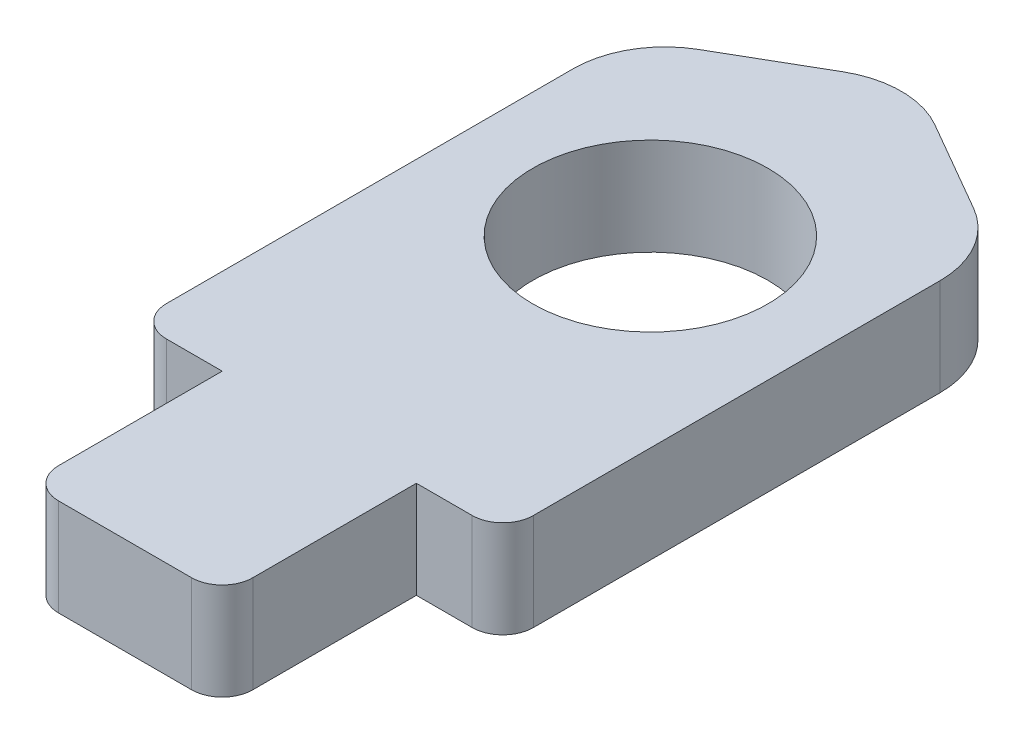
SolidWorks part; units mm, degrees
material "Beech"
ref_plane "Front Plane" through (0, 0, 0) normal (0, 0, 1) x (1, 0, 0)
ref_plane "Top Plane" through (0, 0, 0) normal (0, 1, 0) x (1, 0, 0)
ref_plane "Right Plane" through (0, 0, 0) normal (1, 0, 0) x (0, 0, -1)
sketch "Sketch2" plane through (0, 0, 0) normal (0, 1, 0) x (1, 0, 0)
  line L0 (-6, 5.205) -> (-5.4495, 5.205)
  line L1 (-6, 3.4729) -> (-6, -10.8257)
  line L2 (6, 3.4729) -> (6, -10.8257)
  line L3 (-6, -10.8257) -> (-3.175, -10.8257)
  line L4 (-4.5, 6.071) -> (-1.5, 7.8031)
  line L5 (-3.175, -10.8257) -> (-3.175, -17.1757)
  line L6 (-3.175, -17.1757) -> (3.175, -17.1757)
  line L7 (3.175, -17.1757) -> (3.175, -10.8257)
  line L8 (1.5, 7.8031) -> (4.5, 6.071)
  line L9 (3.175, -10.8257) -> (6, -10.8257)
  line L12 (5.4495, 5.205) -> (6, 5.205)
  circle A0 centre (0, 0) radius 3.845
  arc A1 (-4.5, 6.071) -> (-6, 3.4729) centre (-3, 3.4729) ccw
  arc A2 (4.5, 6.071) -> (6, 3.4729) centre (3, 3.4729) cw
  arc A3 (1.5, 7.8031) -> (-1.5, 7.8031) centre (0, 5.205) ccw
  point P3 (0, 5.205)
  point P14 (0, -17.1757)
  dimension "D1" = 7.69
  dimension "D9" = 3
  dimension "D10" = 3
  dimension "D11" = 3
  dimension "D2" = 5.205
  dimension "D3" = 16.0307
  dimension "D4" = 12
  dimension "D5" = 6.35
  dimension "D6" = 6.35
  dimension "D8" = 30
extrude "MotorMount_Extrude" add sketch "Sketch2" along normal blind 3.175 contours L8 A3 L4 A1 L1 L5 L2 A2 A0 region at (0, 0, 4.7761)
fillet "MotorMount_CornerFillet" radius 1 4 edges at (6, 1.5875, 10.8257) (-6, 1.5875, 10.8257) (-3.175, 1.5875, 17.1757) (3.175, 1.5875, 17.1757)
equation "\"CageLeftBottomEdge\"=22.11mm"
equation "\"CageLeftTopEdge\"=22.11mm"
equation "\"CageRightBottomEdge\"=21.63mm"
equation "\"CageRightTopEdge\"=21.63mm"
equation "\"CageHeight\"=86.04mm"
equation "\"CageLength\"=73.76mm"
equation "\"CageTopScrewClearance\"=10mm"
equation "\"CageBottomScrewClearance\"=25mm"
equation "\"CageLeftTopDepth\"= 11.65mm"
equation "\"CageLeftBottomDepth\"=11.11mm"
equation "\"CageLeftTopHeight\"=8.56175mm"
equation "\"CageLeftBottomHeight\"=16mm"
equation "\"CageRightTopDepth\"= 11.05mm"
equation "\"CageRightBottomDepth\"=10.58mm"
equation "\"CageRightTopHeight\"=9.6mm"
equation "\"CageRightBottomHeight\"=15.49mm"
equation "\"CageLeftTopChannelDepth\"=2.41908mm"
equation "\"CageLeftBottomChannelDepth\"=2.588mm"
equation "\"CageLeftChannelHeight\"=11.7mm"
equation "\"CageRightTopChannelDepth\"=2.32mm"
equation "\"CageRightBottomChannelDepth\"=2.318mm"
equation "\"CageRightChannelHeight\"=10mm"
equation "\"CageChanRelHeight\"=23.99mm"
equation "\"CageChanRelDepth\"=5.492mm"
equation "\"CageChamberRadius\"=16.261mm"
equation "\"CageScrewDiameter\"=4.8mm"
equation "\"CageSetScrewDiameter\"=3.5mm"
equation "\"CageAxleRadius\"=6.639mm"
equation "\"CageAxleKeyHeight\"=1.619mm"
equation "\"CageAxleKeyWidth\"=2.662mm"
equation "\"CageHoseWindowWidth\"=16.29mm"
equation "\"CageHoseWindowHeight\"=26.5mm"
equation "\"CageHoseWindow-Edge\"=8.89mm"
equation "\"CageScrew-VerticalEdge\"=5.0mm"
equation "\"CageScrew-HorizontalEdge\"=7.5mm"
equation "\"CageScrew-HoseCornerScrewEdge\"=4.45mm"
equation "\"CageAxle-BottomEdge\"=56.05mm"
equation "\"CageAxle-FrontEdge\"=46.03mm"
equation "\"CageBackSetScrew-Axle\"=40mm"
equation "\"CageFrontSetScrew-Axle\"=22mm"
equation "\"CageVelocityWindow-BackEdge\"=34.8mm"
equation "\"CageVelocityWindow-BottomEdge\"=27.55mm"
equation "\"CageVelocityWindowHeight\"=22.29mm"
equation "\"CageVelocityWindowWidth\"=12.61mm"
equation "\"TriggerSlot-BottomEdge\"=6.35mm"
equation "\"TriggerSlot-FrontEdge\"=15mm"
equation "\"TriggerSlotSize\"=6.7mm"
equation "\"TriggerRackOffset\"=.236224in"
equation "\"TriggerSlotSizeInt\"=.25in"
equation "\"MotorMountLegLength\"=.25in"
equation "\"GearOffset\"=.264907in"
equation "\"TriggerSlotSpacing\"=.25in"
equation "\"whitemotordepth\"=11.27mm"
equation "\"whitemotorbackdepth\"=3.845mm"
equation "\"whitemotoraxledepth\" = 3.5mm"
equation "\"whitemotoraxleoffset\"=11.4mm"
equation "\"whitemotorwidth\"=12.07mm"
equation "\"whitemotorheight\"=16.68mm"
equation "\"whitemotorcylinderlength\" =13.04mm"
equation "\"whitemotorcylinderradius\"=3.845mm"
equation "\"whitemotorcylinderoffset\"=2.35mm"
equation "\"whitemotorcutoutlength\"=1.88mm"
equation "\"whitemotorouterrad\"=5mm"
equation "\"whitemotorinnerrad\"=2.95mm"
equation "\"D1@Sketch2\"=\"whitemotorcylinderradius\"*2"
equation "\"D2@Sketch2\"=\"whitemotoraxleoffset\"-\"whitemotorcylinderradius\"-\"whitemotorcylinderoffset\""
equation "\"D3@Sketch2\"=\"elasticdepth\"+.005in+\"TriggerRackOffset\"+\"GearOffset\""
equation "\"D5@Sketch2\"=\"TriggerSlotSizeInt\""
equation "\"D6@Sketch2\"=\"MotorMountLegLength\""
equation "\"motormountwidth\"=12mm"
equation "\"D4@Sketch2\"=\"motormountwidth\""
equation "\"TriggerMiniSlotWidth\"=3.5mm"
equation "\"TriggerRackWidth\"=6.5mm"
equation "\"elasticracklength\"=2in"
equation "\"elasticrackpegsize\"=.25in"
equation "\"elasticrackpegbuffer\"=.125in"
equation "\"elasticrackpegspacing\"=1.76476378in"
equation "\"elasticbaybuffer\"=.25in"
equation "\"elasticdepth\"=.125in"
equation "\"motormountcornerfillet\"=3mm"
equation "\"D10@Sketch2\"=\"motormountcornerfillet\""
equation "\"elasticbaydepth\"=.75in"
equation "\"pandiscradius\"=14in"
equation "\"towermaterialwidth\"=.25in"
equation "\"towerslotlength\"=.5in"
equation "\"towermarkerspace\"=5in"
equation "\"towerslothorizoffset\"=1in"
equation "\"towerslothorizspacing\"=2in"
equation "\"towerslotvertoffset\"=3in"
equation "\"towerslotvertspacing\"=1in"
equation "\"towerheight\"=12in"
equation "\"towerupslot\"=1in"
equation "\"toweraxle\"=.5in"
equation "\"stepperouterrad\"=10mm"
equation "\"stepperscrewsize\"=3.45mm"
equation "\"stepperscrewc2c\"=49.5mm"
equation "\"stepperdepthoffset\"=24mm"
equation "\"stepperhorizoffset\"=22.91mm"
equation "\"shaftslotOD\"=18.8mm"
equation "\"shaftslotID\"=13.28mm"
equation "\"shaftkeywidth\"=2.67mm"
equation "\"shaftkeydepth\"=1.8mm"
equation "\"shaftcollartotaldepth\"=12.5mm"
equation "\"shaftsquaredepth\"=6mm"
equation "\"shaftsetscrewsize\"=3.5mm"
equation "\"shaftkeytightdepth\"=1.85mm"
equation "\"shaftslottightID\"=12.78mm"
equation "\"shaftsetscrewoffset\"=9mm"
equation "\"cagecollartotaldepth\"=10mm"
equation "\"cagecollartotalwidth\"=35mm"
equation "\"cagecollarbasedepth\"=4mm"
equation "\"gearhubintdiam\"=30mm"
equation "\"gearhubintwid\"=15mm"
equation "\"towerspeedwidth\"=2in"
equation "\"towerspeedheight\"=8in"
equation "\"towerspeedgap\"=2in"
equation "\"stepperaxleflat\"=.037in"
equation "\"stepperaxlerad\"=0.11811024in"
equation "\"ajaxaxlesize\"=3.87mm"
equation "\"ajaxinnercut\"=2.3mm"
equation "\"ajaxwidth\"=6.1mm"
equation "\"ajaxdiametral\"=25.8854"
equation "\"ajaxcutoutdepth\"=2.3mm"
equation "\"ajax4020gap\"=29.5mm"
equation "\"ajax4010gap\"=24.5mm"
equation "\"ajax20hubbuffer\"=6.1mm"
equation "\"ajax20hubholeoffset\"=.19685in"
equation "\"ajax20hubholesize\"=.059055in"
equation "\"ajax20cutoutint\"=13.4mm"
equation "\"ajax40hubholesize\"=7.21mm"
equation "\"ajax40hubholeoffset\"=10mm"
equation "\"ajax40hubbuffer\"=8.9mm"
equation "\"ajax40cutoutint\"=32.6mm"
equation "\"bearingpandiscrad\"=6.8in"
equation "\"bearingpandiscang\"=48.75deg"
equation "\"bearingclearholedist\"=4.7345in"
equation "\"bearingclearholesize\"=.5in"
equation "\"bearingclearholeang\"=22.5deg"
equation "\"bearingmountholedist\"=4.25in"
equation "\"bearingwirehole\"=1.5in"
equation "\"no6diam\"=.146in"
equation "\"shortconangle\"=20deg"
equation "\"shortconlen\"=.875in"
equation "\"longconlen\"=1.25in"
equation "\"longconangle\"=15deg"
